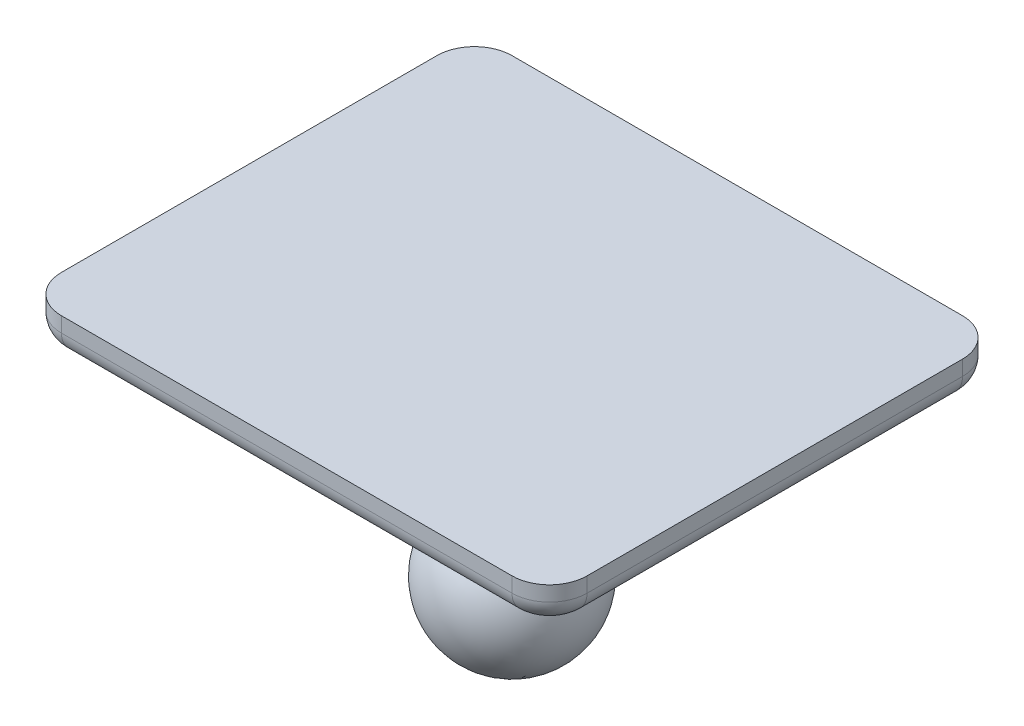
SolidWorks part; units mm, degrees
ref_plane "Front Plane" through (0, 0, 0) normal (0, 0, 1) x (1, 0, 0)
ref_plane "Top Plane" through (0, 0, 0) normal (0, 1, 0) x (1, 0, 0)
ref_plane "Right Plane" through (0, 0, 0) normal (1, 0, 0) x (0, 0, -1)
sketch "Sketch1" plane through (0, 0, 0) normal (0, 1, 0) x (1, 0, 0)
  line L0 (0, -9.75) -> (0, 9.75)
  arc A0 (0, 9.75) -> (0, -9.75) centre (0, 0) ccw
  point P6 (0, 0)
  dimension "D1" = 19.5
revolve "Revolve1" add sketch "Sketch1" angle 360 about L0
sketch "Sketch2" plane through (0, 0, 0) normal (0, 1, 0) x (1, 0, 0)
  line L1 (0.5, -4) -> (-0.5, -4)
  line L2 (0.5, -4) -> (0.5, 4)
  line L3 (0.5, 4) -> (-0.5, 4)
  line L4 (-0.5, -4) -> (-0.5, 4)
  line L5 (0.5, -4) -> (-0.5, 4) construction
  line L6 (0.5, 4) -> (-0.5, -4) construction
  point P0 (0, 0)
  dimension "D1" = 1
  dimension "D2" = 8
ref_plane "Plane1" through (0, 25, 0) normal (0, 1, 0) x (1, 0, 0)
sketch "Sketch3" plane through (0, 25, 0) normal (0, 1, 0) x (1, 0, 0)
  line L1 (-5, -7.5) -> (5, -7.5)
  line L2 (-5, -7.5) -> (-5, 7.5)
  line L3 (-5, 7.5) -> (5, 7.5)
  line L4 (5, -7.5) -> (5, 7.5)
  line L5 (-5, -7.5) -> (5, 7.5) construction
  line L6 (-5, 7.5) -> (5, -7.5) construction
  point P0 (0, 0)
  dimension "D1" = 15
  dimension "D2" = 10
loft "Loft1" add profiles "Sketch2", "Sketch3"
sketch "Sketch4" plane through (0, 25, 0) normal (0, 1, 0) x (1, 0, 0)
  line L1 (-35, -30) -> (35, -30)
  line L2 (-35, -30) -> (-35, 30)
  line L3 (-35, 30) -> (35, 30)
  line L4 (35, -30) -> (35, 30)
  line L5 (-35, -30) -> (35, 30) construction
  line L6 (-35, 30) -> (35, -30) construction
  point P0 (0, 0)
  dimension "D1" = 60
  dimension "D2" = 70
extrude "Boss-Extrude1" add sketch "Sketch4" along normal blind 5
fillet "Fillet2" radius 2 4 edges at (-2.2093, 9.4964, 0) (0, 8.2737, -5.1583) (2.2093, 9.4964, 0) (0, 8.2737, 5.1583)
fillet "Fillet3" radius 2 12 edges at (-2.4468, 8.4947, 5.3011) (-2.4468, 8.4947, -5.3011) (2.4468, 8.4947, 5.3011) (2.4468, 8.4947, -5.3011)
fillet "Fillet4" radius 3 4 edges at (-35, 25, 0) (0, 25, 30) (0, 25, -30) (35, 25, 0)
fillet "Fillet5" radius 5 8 edges at (34.1213, 25.8787, -29.1213) (34.1213, 25.8787, 29.1213) (-34.1213, 25.8787, 29.1213) (-34.1213, 25.8787, -29.1213) (35, 29, -30) (35, 29, 30) (-35, 29, 30) (-35, 29, -30)
fillet "Fillet6" radius 11 8 edges at (4.4223, 25, 6.9259) (-4.4223, 25, 6.9259) (-4.4223, 25, -6.9259) (4.4223, 25, -6.9259)
sketch "Sketch6" plane through (0, 0, 0) normal (0, 0, 1) x (1, 0, 0)
  line L0 (-20, 25) -> (-20, 24)
  line L1 (30, 25) -> (-30, 25) construction
  line L2 (-21, 25) -> (-21, 24)
  line L3 (-21.494, 22.6428) -> (-20.7279, 22)
  line L4 (-35, 28) -> (-35, 30) construction
  line L5 (-23.1114, 24) -> (-21.494, 22.6428) construction
  line L6 (-20, 25) -> (-21, 25)
  arc A0 (-20, 24) -> (-20.7279, 22) centre (-23.1114, 24) cw
  arc A1 (-21, 24) -> (-21.494, 22.6428) centre (-23.1114, 24) cw
  arc A2 (-20, 24) -> (-20.7279, 22) centre (-23.1114, 24) cw construction
  dimension "D5" = 2
  dimension "D2" = 1
  dimension "D3" = 40
  dimension "D4" = 15
  dimension "D1" = 1
extrude "Boss-Extrude2" add sketch "Sketch6" along normal mid plane 15
ref_plane "Plane2" through (-23, 0, 0) normal (-1, 0, 0) x (0, 0, 1)
mirror "Mirror1" about plane through (-23, 0, 0) normal (-1, 0, 0) of "Boss-Extrude2"
